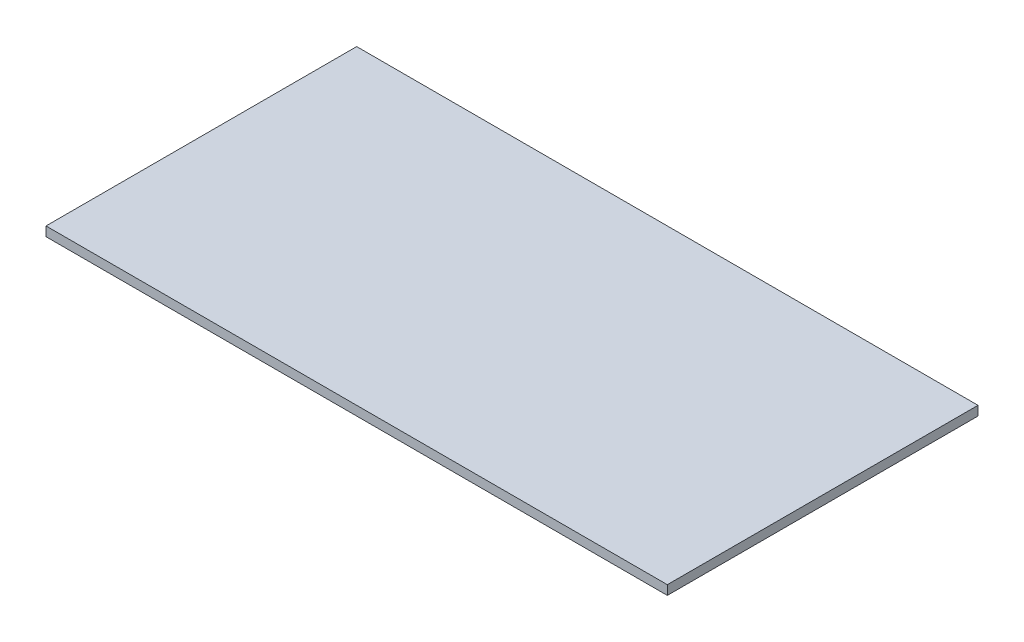
SolidWorks part; units mm, degrees
ref_plane "Front Plane" through (0, 0, 0) normal (0, 0, 1) x (1, 0, 0)
ref_plane "Top Plane" through (0, 0, 0) normal (0, 1, 0) x (1, 0, 0)
ref_plane "Right Plane" through (0, 0, 0) normal (1, 0, 0) x (0, 0, -1)
sketch "Sketch1" plane through (0, 0, 0) normal (0, 1, 0) x (1, 0, 0)
  line L1 (-100, 50) -> (100, 50)
  line L2 (-100, 50) -> (-100, -50)
  line L3 (-100, -50) -> (100, -50)
  line L4 (100, 50) -> (100, -50)
  line L5 (-100, 50) -> (100, -50) construction
  line L6 (-100, -50) -> (100, 50) construction
  point P0 (0, 0)
  point P6 (0, 0)
  dimension "D1" = 200
  dimension "D2" = 100
extrude "Boss-Extrude1" add sketch "Sketch1" along normal blind 3
equation "\"car_length\" = 200"
equation "\"car_width\"= 100"
equation "\"platform_width\"= 3"
equation "\"D1@Sketch1\"=\"car_length\""
equation "\"D2@Sketch1\"=\"car_width\""
equation "\"D1@Boss-Extrude1\"=\"platform_width\""
